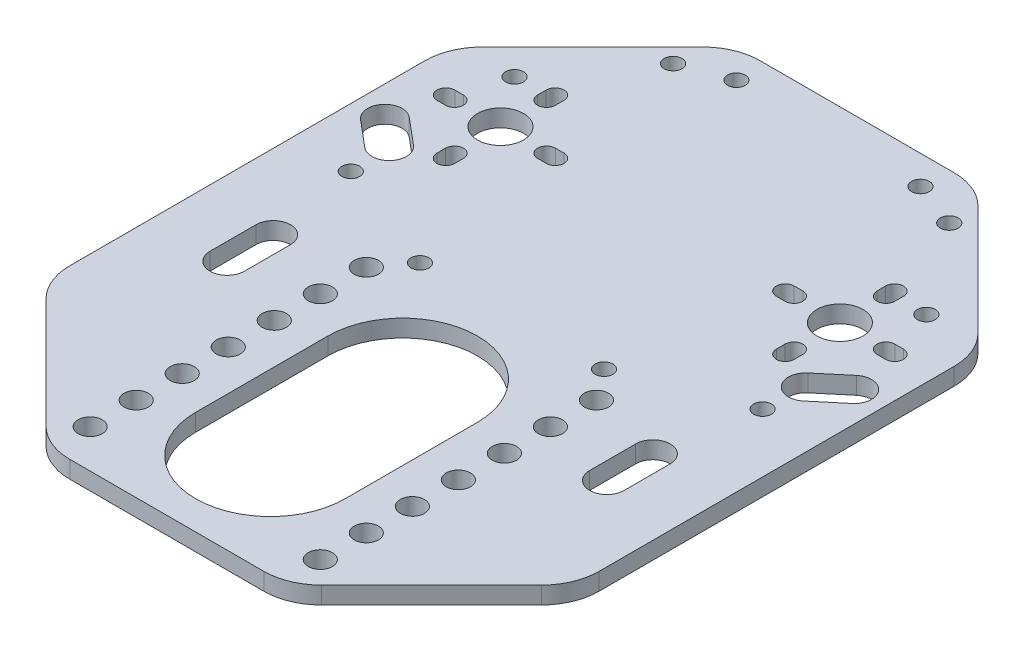
SolidWorks part; units mm, degrees
material "Thornel Mat VMA"
ref_plane "Front Plane" through (0, 0, 0) normal (0, 0, 1) x (1, 0, 0)
ref_plane "Top Plane" through (0, 0, 0) normal (0, 1, 0) x (1, 0, 0)
ref_plane "Right Plane" through (0, 0, 0) normal (1, 0, 0) x (0, 0, -1)
sketch "Sketch1" plane through (0, 0, 0) normal (0, 1, 0) x (1, 0, 0)
  line L0 (0, 0) -> (0, -275.7813) construction
  line L1 (0, 0) -> (121.6069, 0) construction
  line L2 (37.5, 0) -> (39, 0) construction
  line L3 (37.5, 1.55) -> (39, 1.55)
  line L4 (37.5, -1.55) -> (39, -1.55)
  line L5 (29.5, -8) -> (29.5, -9.5) construction
  line L6 (31.05, -8) -> (31.05, -9.5)
  line L7 (27.95, -8) -> (27.95, -9.5)
  line L8 (21.5, 0) -> (20, 0) construction
  line L9 (21.5, -1.55) -> (20, -1.55)
  line L10 (21.5, 1.55) -> (20, 1.55)
  line L11 (29.5, 8) -> (29.5, 9.5) construction
  line L12 (27.95, 8) -> (27.95, 9.5)
  line L13 (31.05, 8) -> (31.05, 9.5)
  line L14 (41, -25) -> (41, -67.0317) construction
  line L15 (-46, 32.5) -> (46, 32.5)
  line L16 (46, 32.5) -> (46, -153.73)
  line L17 (46, -153.73) -> (-46, -153.73)
  line L18 (-46, 32.5) -> (-46, -153.73)
  line L19 (-29.5, 8) -> (-29.5, 9.5) construction
  line L20 (-27.95, 8) -> (-27.95, 9.5)
  line L21 (-31.05, 8) -> (-31.05, 9.5)
  line L22 (-21.5, 0) -> (-20, 0) construction
  line L23 (-21.5, -1.55) -> (-20, -1.55)
  line L24 (-21.5, 1.55) -> (-20, 1.55)
  line L25 (-29.5, -8) -> (-29.5, -9.5) construction
  line L26 (-31.05, -8) -> (-31.05, -9.5)
  line L27 (-27.95, -8) -> (-27.95, -9.5)
  line L28 (-37.5, 0) -> (-39, 0) construction
  line L29 (-37.5, 1.55) -> (-39, 1.55)
  line L30 (-37.5, -1.55) -> (-39, -1.55)
  line L31 (0, -46.5) -> (0, -69.5) construction
  line L32 (13, -46.5) -> (13, -69.5)
  line L33 (-13, -46.5) -> (-13, -69.5)
  line L34 (0, -69.5) -> (-54.3785, -44.1429) construction
  line L35 (0, -69.5) -> (-45.0064, -85.881) construction
  line L36 (12.327, -114.5) -> (110.2373, -114.5) construction
  line L37 (5, -92.7422) -> (5, -214.7614) construction
  line L38 (29.5, 0) -> (50.8627, -25.4591) construction
  line L41 (40.7972, -8.7963) -> (36.2009, -12.653) construction
  line L42 (42.7255, -11.0944) -> (38.1293, -14.9511)
  line L43 (38.8688, -6.4981) -> (34.2725, -10.3549)
  line L44 (-40.7972, -8.7963) -> (-36.2009, -12.653) construction
  line L45 (-42.7255, -11.0944) -> (-38.1293, -14.9511)
  line L46 (-38.8688, -6.4981) -> (-34.2725, -10.3549)
  line L47 (33, -36) -> (33, -44) construction
  line L48 (36, -36) -> (36, -44)
  line L49 (30, -36) -> (30, -44)
  line L50 (-33, -36) -> (-33, -44) construction
  line L51 (-36, -36) -> (-36, -44)
  line L52 (-30, -36) -> (-30, -44)
  line L53 (15, -149.73) -> (35, -149.73) construction
  line L54 (15, -148.18) -> (35, -148.18)
  line L55 (15, -151.28) -> (35, -151.28)
  line L56 (-15, -149.73) -> (-35, -149.73) construction
  line L57 (-15, -148.18) -> (-35, -148.18)
  line L58 (-15, -151.28) -> (-35, -151.28)
  line L59 (-959, -57) -> (49041, -57) construction
  circle A0 centre (29.5, 0) radius 4
  arc A1 (37.5, 1.55) -> (37.5, -1.55) centre (37.5, 0) ccw
  arc A2 (39, -1.55) -> (39, 1.55) centre (39, 0) ccw
  arc A3 (31.05, -8) -> (27.95, -8) centre (29.5, -8) ccw
  arc A4 (27.95, -9.5) -> (31.05, -9.5) centre (29.5, -9.5) ccw
  arc A5 (21.5, -1.55) -> (21.5, 1.55) centre (21.5, 0) ccw
  arc A6 (20, 1.55) -> (20, -1.55) centre (20, 0) ccw
  arc A7 (27.95, 8) -> (31.05, 8) centre (29.5, 8) ccw
  arc A8 (31.05, 9.5) -> (27.95, 9.5) centre (29.5, 9.5) ccw
  circle A9 centre (41, -25) radius 1.55 construction
  circle A13 centre (-29.5, 0) radius 4
  arc A14 (-27.95, 8) -> (-31.05, 8) centre (-29.5, 8) cw
  arc A15 (-31.05, 9.5) -> (-27.95, 9.5) centre (-29.5, 9.5) cw
  arc A16 (-21.5, -1.55) -> (-21.5, 1.55) centre (-21.5, 0) cw
  arc A17 (-20, 1.55) -> (-20, -1.55) centre (-20, 0) cw
  arc A18 (-31.05, -8) -> (-27.95, -8) centre (-29.5, -8) cw
  arc A19 (-27.95, -9.5) -> (-31.05, -9.5) centre (-29.5, -9.5) cw
  arc A20 (-37.5, 1.55) -> (-37.5, -1.55) centre (-37.5, 0) cw
  arc A21 (-39, -1.55) -> (-39, 1.55) centre (-39, 0) cw
  circle A22 centre (16, 27.5) radius 1.55
  circle A23 centre (16, -27.5) radius 1.55
  circle A24 centre (-16, -27.5) radius 1.55
  circle A25 centre (-16, 27.5) radius 1.55
  circle A26 centre (-27.1892, -56.8215) radius 1.55 construction
  circle A27 centre (-28.1908, -79.7606) radius 1.55 construction
  circle A28 centre (28.1908, -79.7606) radius 1.55 construction
  circle A29 centre (27.1892, -56.8215) radius 1.55 construction
  arc A30 (13, -46.5) -> (-13, -46.5) centre (0, -46.5) ccw
  arc A31 (-13, -69.5) -> (13, -69.5) centre (0, -69.5) ccw
  circle A36 centre (40.79, -100.27) radius 1.55
  circle A37 centre (40.79, -128.73) radius 1.55
  circle A38 centre (-30.79, -128.73) radius 1.55
  circle A39 centre (-30.79, -100.27) radius 1.55
  circle A45 centre (41, -33) radius 1.55 construction
  circle A46 centre (41, -41) radius 1.55 construction
  circle A47 centre (41, -49) radius 1.55 construction
  circle A48 centre (41, -57) radius 1.55 construction
  circle A49 centre (41, -65) radius 1.55 construction
  circle A50 centre (41, -73) radius 1.55 construction
  circle A51 centre (41, -81) radius 1.55 construction
  circle A52 centre (-41, -81) radius 1.55 construction
  circle A53 centre (-41, -73) radius 1.55 construction
  circle A54 centre (-41, -65) radius 1.55 construction
  circle A55 centre (-41, -57) radius 1.55 construction
  circle A56 centre (-41, -49) radius 1.55 construction
  circle A57 centre (-41, -41) radius 1.55 construction
  circle A58 centre (-41, -33) radius 1.55 construction
  circle A59 centre (-41, -25) radius 1.55 construction
  arc A60 (42.7255, -11.0944) -> (38.8688, -6.4981) centre (40.7972, -8.7963) ccw
  arc A61 (34.2725, -10.3549) -> (38.1293, -14.9511) centre (36.2009, -12.653) ccw
  arc A62 (-42.7255, -11.0944) -> (-38.8688, -6.4981) centre (-40.7972, -8.7963) cw
  arc A63 (-34.2725, -10.3549) -> (-38.1293, -14.9511) centre (-36.2009, -12.653) cw
  arc A64 (36, -36) -> (30, -36) centre (33, -36) ccw
  arc A65 (30, -44) -> (36, -44) centre (33, -44) ccw
  arc A66 (-36, -36) -> (-30, -36) centre (-33, -36) cw
  arc A67 (-30, -44) -> (-36, -44) centre (-33, -44) cw
  arc A68 (15, -148.18) -> (15, -151.28) centre (15, -149.73) ccw
  arc A69 (35, -151.28) -> (35, -148.18) centre (35, -149.73) ccw
  arc A70 (-15, -148.18) -> (-15, -151.28) centre (-15, -149.73) cw
  arc A71 (-35, -151.28) -> (-35, -148.18) centre (-35, -149.73) cw
  circle A72 centre (24, 24.5) radius 1.55
  circle A73 centre (-24, 24.5) radius 1.55
  circle A74 centre (41, -146.73) radius 1.55
  circle A75 centre (-41, -146.73) radius 1.55
  point P8 (38.25, 0)
  point P18 (29.5, -8.75)
  point P25 (20.75, 0)
  point P32 (29.5, 8.75)
  point P37 (29.5, 0)
  point P50 (0, -153.73)
  point P51 (0, 32.5)
  point P55 (-29.5, 8.75)
  point P62 (-20.75, 0)
  point P69 (-29.5, -8.75)
  point P76 (-38.25, 0)
  point P98 (0, -58)
  point P145 (38.499, -10.7246)
  point P152 (-38.499, -10.7246)
  point P159 (33, -40)
  point P166 (-33, -40)
  point P173 (25, -149.73)
  point P180 (-25, -149.73)
  dimension "D1" = 8
  dimension "D2" = 1.55
  dimension "D4" = 8
  dimension "D5" = 4
  dimension "D6" = 3.1
  dimension "D7" = 25
  dimension "D8" = 41
  dimension "D9" = 59
  dimension "D10" = 3.1
  dimension "D11" = 16
  dimension "D12" = 27.5
  dimension "D13" = 13
  dimension "D15" = 30
  dimension "D18" = 46.5
  dimension "D19" = 5
  dimension "D20" = 8
  dimension "D21" = 45
  dimension "D25" = 14.23
  dimension "D26" = 35.79
  dimension "D27" = 3
  dimension "D30" = 25
  dimension "D33" = 3
  dimension "D36" = 1.55
  dimension "D40" = 8
  dimension "D41" = 3
  dimension "D42" = 5
  dimension "D43" = 7
  dimension "D3" = 1.5
  dimension "D14" = 23
  dimension "D16" = 30
  dimension "D17" = 70
  dimension "D22" = 45
  dimension "D23" = 50
  dimension "D24" = 5
  dimension "D28" = 14
  dimension "D29" = 6
  dimension "D31" = 5
  dimension "D32" = 8
  dimension "D34" = 8
  dimension "D35" = 40
  dimension "D37" = 20
  dimension "D38" = 4
  dimension "D39" = 25
extrude "Boss-Extrude1" add sketch "Sketch1" along normal blind 3
chamfer "Chamfer1" distance 25 angle 45 2 edges at (46, 1.5, -32.5) (-46, 1.5, -32.5)
fillet "Fillet1" radius 10 6 edges at (-46, 1.5, 153.73) (46, 1.5, 153.73) (46, 1.5, -7.5) (21, 1.5, -32.5) (-46, 1.5, -7.5) (-21, 1.5, -32.5)
sketch "草图2" plane through (0, 3, 0) normal (0, 1, 0) x (1, 0, 0)
  line L0 (-13, -46.5) -> (-13, -69.5) construction
  line L1 (-27.1892, -56.8215) -> (-46, -56.8215) construction
  line L2 (-46, 3.3579) -> (-46, -143.73) construction
  line L4 (-20, -56.8215) -> (-20, -30.9859) construction
  line L5 (0, -1000) -> (0, 49000) construction
  line L6 (20, -56.8215) -> (20, -30.9859) construction
  circle A3 centre (-27.1892, -56.8215) radius 1.55 construction
  circle A4 centre (-27.1892, -56.8215) radius 1.55 construction
  circle A5 centre (-20, -56.8215) radius 2.1
  circle A6 centre (-20, -48.8215) radius 2.1
  circle A7 centre (-20, -40.8215) radius 2.1
  circle A8 centre (-20, -32.8215) radius 2.1
  circle A9 centre (-20, -64.8215) radius 2.1
  circle A10 centre (-20, -72.8215) radius 2.1
  circle A11 centre (-20, -80.8215) radius 2.1
  circle A12 centre (20, -80.8215) radius 2.1
  circle A13 centre (20, -72.8215) radius 2.1
  circle A14 centre (20, -64.8215) radius 2.1
  circle A15 centre (20, -32.8215) radius 2.1
  circle A16 centre (20, -40.8215) radius 2.1
  circle A17 centre (20, -48.8215) radius 2.1
  circle A18 centre (20, -56.8215) radius 2.1
  dimension "D1" = 4.2
  dimension "D2" = 7
  dimension "D3" = 4
  dimension "D4" = 4
extrude "切除-拉伸2" cut sketch "草图2" against normal blind 10
sketch "草图5" plane through (0, 3, 0) normal (0, 1, 0) x (1, 0, 0)
  line L0 (-46, -87.5) -> (46, -87.5)
  line L1 (-46, 3.3579) -> (-46, -143.73) construction
  line L2 (46, -143.73) -> (46, 3.3579) construction
  line L3 (16.8579, 32.5) -> (-16.8579, 32.5) construction
  line L5 (-46, 3.3579) -> (-46, -143.73) construction
  line L6 (-46, 3.3579) -> (-46, -143.73)
  line L8 (46, -143.73) -> (46, 3.3579) construction
  line L9 (46, -143.73) -> (46, 3.3579)
  line L10 (-36, -153.73) -> (36, -153.73) construction
  line L11 (-36, -153.73) -> (36, -153.73)
  arc A0 (36, -153.73) -> (46, -143.73) centre (36, -143.73) ccw construction
  arc A1 (-46, -143.73) -> (-36, -153.73) centre (-36, -143.73) ccw construction
  arc A2 (36, -153.73) -> (46, -143.73) centre (36, -143.73) ccw
  arc A3 (-46, -143.73) -> (-36, -153.73) centre (-36, -143.73) ccw
  dimension "D1" = 120
extrude "切除-拉伸3" cut sketch "草图5" against normal blind 10 contours L0 region at (0, 3, 120.3959)
chamfer "倒角1" distance 25 angle 45 2 edges at (46, 1.5, 87.5) (-46, 1.5, 87.5)
fillet "圆角1" radius 10 4 edges at (46, 1.5, 62.5) (21, 1.5, 87.5) (-21, 1.5, 87.5) (-46, 1.5, 62.5)
sketch "草图6" plane through (0, 3, 0) normal (0, 1, 0) x (1, 0, 0)
  line L0 (0, 0) -> (0, 38.5934) construction
  line L1 (16.8579, 32.5) -> (-16.8579, 32.5) construction
  line L2 (-35.79, 8.73) -> (35.79, 8.73) construction
  line L3 (-35.79, 8.73) -> (-35.79, -19.73) construction
  line L4 (-35.79, -19.73) -> (35.79, -19.73) construction
  line L5 (35.79, 8.73) -> (35.79, -19.73) construction
  line L6 (-35.79, 8.73) -> (35.79, -19.73) construction
  line L7 (-35.79, -19.73) -> (35.79, 8.73) construction
  circle A0 centre (-35.79, 8.73) radius 1.55
  circle A1 centre (35.79, 8.73) radius 1.55
  circle A2 centre (35.79, -19.73) radius 1.55
  circle A3 centre (-35.79, -19.73) radius 1.55
  point P3 (0, -5.5)
  dimension "D4" = 3.1
  dimension "D5" = 3.1
  dimension "D6" = 3.1
  dimension "D7" = 3.1
  dimension "D1" = 28.46
  dimension "D2" = 71.58
  dimension "D3" = 38
extrude "切除-拉伸4" cut sketch "草图6" against normal blind 10
